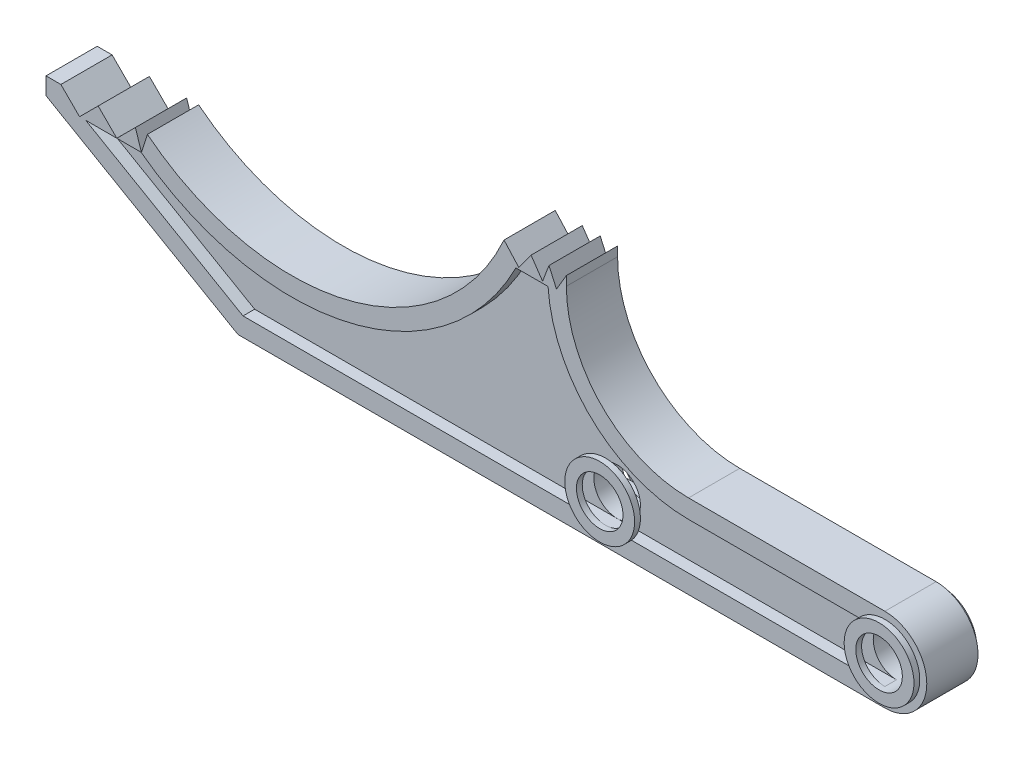
SolidWorks part; units mm, degrees
ref_plane "Front Plane" through (0, 0, 0) normal (0, 0, 1) x (1, 0, 0)
ref_plane "Top Plane" through (0, 0, 0) normal (0, 1, 0) x (1, 0, 0)
ref_plane "Right Plane" through (0, 0, 0) normal (1, 0, 0) x (0, 0, -1)
sketch "Sketch1" plane through (0, 0, 0) normal (0, 0, 1) x (1, 0, 0)
  line L0 (0, 0) -> (70, 0)
  line L1 (0, 0) -> (-22.0836, 12.75)
  line L2 (-22.0836, 12.75) -> (-22.0836, 17.75)
  line L3 (-22.0836, 17.75) -> (-8.4836, 17.75)
  line L4 (27.7864, 27.12) -> (37.7964, 27.12)
  line L5 (70, 0) -> (70, 13) construction
  line L6 (70, 13) -> (48.9164, 13)
  line L7 (37.7964, 27.12) -> (37.7964, 24.12)
  arc A0 (27.7864, 27.12) -> (-8.4836, 17.75) centre (6.3126, 35.3588) cw
  arc A1 (70, 0) -> (70, 13) centre (70, 6.5) ccw
  arc A3 (37.7964, 24.12) -> (48.9164, 13) centre (48.9164, 24.12) ccw
  point P14 (0, 0)
  point P15 (0, 0)
  point P16 (42.0343, 22.6471)
  point P17 (47.0472, 25.7525)
  dimension "D9" = 23
  dimension "D1" = 70
  dimension "D2" = 210
  dimension "D3" = 25.5
  dimension "D4" = 5
  dimension "D5" = 13.6
  dimension "D6" = 27.12
  dimension "D7" = 10.01
  dimension "D8" = 36.27
  dimension "D10" = 13
  dimension "D11" = 3
extrude "Boss-Extrude1" add sketch "Sketch1" along normal mid plane 8
sketch "Sketch3" plane through (0, 0, -4) normal (0, 0, -1) x (-1, 0, 0)
  line L0 (-70, 6.5) -> (-40, 6.5) construction
  circle A2 centre (-70, 6.5) radius 2.5
  circle A3 centre (-40, 6.5) radius 2.5
  dimension "D1" = 5
  dimension "D2" = 5
  dimension "D3" = 30
extrude "Cut-Extrude1" cut sketch "Sketch3" against normal through all
sketch "Sketch4" plane through (0, 0, 4) normal (0, 0, 1) x (1, 0, 0)
  line L14 (-20.0836, 13.9047) -> (0.5359, 2)
  line L15 (0.5359, 2) -> (70, 2)
  line L16 (70, 11) -> (48.9164, 11)
  line L17 (35.7964, 24.12) -> (35.7964, 25.12)
  line L18 (35.7964, 25.12) -> (29.1198, 25.12)
  line L19 (-9.1953, 15.75) -> (-20.0836, 15.75)
  line L20 (-20.0836, 15.75) -> (-20.0836, 13.9047)
  line L21 (-20.0836, 13.9047) -> (0.5359, 2)
  line L22 (0.5359, 2) -> (70, 2)
  line L23 (70, 11) -> (48.9164, 11)
  line L24 (35.7964, 24.12) -> (35.7964, 25.12)
  line L25 (35.7964, 25.12) -> (29.1198, 25.12)
  line L26 (-9.1953, 15.75) -> (-20.0836, 15.75)
  line L27 (-20.0836, 15.75) -> (-20.0836, 13.9047)
  arc A6 (70, 2) -> (70, 11) centre (70, 6.5) ccw
  arc A7 (35.7964, 24.12) -> (48.9164, 11) centre (48.9164, 24.12) ccw
  arc A8 (-9.1953, 15.75) -> (29.1198, 25.12) centre (6.3126, 35.3588) ccw
  arc A9 (70, 2) -> (70, 11) centre (70, 6.5) ccw
  arc A10 (35.7964, 24.12) -> (48.9164, 11) centre (48.9164, 24.12) ccw
  arc A11 (-9.1953, 15.75) -> (29.1198, 25.12) centre (6.3126, 35.3588) ccw
  dimension "D1" = 2
extrude "Cut-Extrude2" cut sketch "Sketch4" against normal blind 1.25
sketch "Sketch5" plane through (0, 0, 2.75) normal (0, 0, 1) x (1, 0, 0)
  circle A0 centre (70, 6.5) radius 2.5 construction
  circle A1 centre (70, 6.5) radius 2.5
  circle A2 centre (40, 6.5) radius 2.5 construction
  circle A3 centre (40, 6.5) radius 2.5
  circle A4 centre (40, 6.5) radius 3.75
  circle A5 centre (70, 6.5) radius 3.75
  dimension "D1" = 1.25
extrude "Boss-Extrude2" add sketch "Sketch5" along normal mid plane 1.25
mirror "Mirror1" about plane through (0, 0, 0) normal (0, 0, 1) of "Cut-Extrude2", "Boss-Extrude2"
sketch "Sketch7" plane through (0, 0, 4) normal (0, 0, 1) x (1, 0, 0)
  line L0 (-22.0836, 17.75) -> (-20.4836, 17.75) construction
  line L1 (-8.4836, 17.75) -> (-22.0836, 17.75) construction
  line L2 (-20.4836, 17.75) -> (-18.4836, 15.75) construction
  line L3 (-9.1953, 15.75) -> (-20.0836, 15.75) construction
  line L4 (-18.4836, 15.75) -> (-16.4836, 17.75) construction
  line L5 (-16.4836, 17.75) -> (-16.4836, 12.6303) construction
  line L6 (-14.4836, 15.75) -> (-16.4836, 17.75) construction
  line L7 (-12.4836, 17.75) -> (-14.4836, 15.75) construction
  line L8 (-12.4836, 17.75) -> (-12.4836, 11.9186) construction
  line L9 (-12.4836, 17.75) -> (-10.4836, 15.75) construction
  line L10 (-10.4836, 15.75) -> (-8.4836, 17.75) construction
  line M5 (0.5359, 2) -> (-20.0836, 13.9047)
  line M6 (-20.0836, 13.9047) -> (-20.0836, 15.75)
  line M7 (-20.0836, 15.75) -> (-9.1953, 15.75)
  arc M8 (-9.1953, 15.75) -> (29.1198, 25.12) centre (6.3126, 35.3588) ccw
  line M9 (29.1198, 25.12) -> (35.7964, 25.12)
  line M10 (35.7964, 25.12) -> (35.7964, 24.12)
  arc M11 (35.7964, 24.12) -> (48.9164, 11) centre (48.9164, 24.12) ccw
  line M12 (48.9164, 11) -> (70, 11)
  arc M13 (70, 11) -> (70, 2) centre (70, 6.5) cw
  line M14 (70, 2) -> (0.5359, 2)
  line M15 (-22.0836, 12.75) -> (0, 0)
  line M16 (0, 0) -> (70, 0)
  arc M17 (70, 0) -> (70, 13) centre (70, 6.5) ccw
  line M18 (70, 13) -> (48.9164, 13)
  arc M19 (48.9164, 13) -> (37.7964, 24.12) centre (48.9164, 24.12) cw
  line M20 (37.7964, 24.12) -> (37.7964, 27.12)
  line M21 (37.7964, 27.12) -> (27.7864, 27.12)
  arc M22 (27.7864, 27.12) -> (-8.4836, 17.75) centre (6.3126, 35.3588) cw
  line M23 (-8.4836, 17.75) -> (-22.0836, 17.75)
  line M24 (-22.0836, 17.75) -> (-22.0836, 12.75)
  dimension "D1" = 1.6
  dimension "D2" = 90
  dimension "D3" = 135
  dimension "D4" = 2.8284
extrude "Cut-Extrude3" cut sketch "Sketch7" against normal through all contours M24 M15 M16 M17 M18 M19 M20 M21 M22 M23 M14 M5 M6 M7 M8 M9 M10 M11 M12 M13 region at (-21.0612, 15.25, 4)
sketch "Sketch8" plane through (0, 0, 2.75) normal (0, 0, 1) x (1, 0, 0)
  line L14 (-15.8157, 13.75) -> (1.0718, 4)
  line L15 (1.0718, 4) -> (70, 4)
  line L16 (70, 9) -> (48.9164, 9)
  line L17 (33.8295, 23.12) -> (30.3794, 23.12)
  line L18 (-9.8756, 13.75) -> (-15.8157, 13.75)
  line L19 (-15.8157, 13.75) -> (1.0718, 4)
  line L20 (1.0718, 4) -> (70, 4)
  line L21 (70, 9) -> (48.9164, 9)
  line L22 (33.8295, 23.12) -> (30.3794, 23.12)
  line L23 (-9.8756, 13.75) -> (-15.8157, 13.75)
  arc A6 (70, 4) -> (70, 9) centre (70, 6.5) ccw
  arc A7 (33.8295, 23.12) -> (48.9164, 9) centre (48.9164, 24.12) ccw
  arc A8 (-9.8756, 13.75) -> (30.3794, 23.12) centre (6.3126, 35.3588) ccw
  arc A9 (70, 4) -> (70, 9) centre (70, 6.5) ccw
  arc A10 (33.8295, 23.12) -> (48.9164, 9) centre (48.9164, 24.12) ccw
  arc A11 (-9.8756, 13.75) -> (30.3794, 23.12) centre (6.3126, 35.3588) ccw
  dimension "D1" = 2
extrude "Cut-Extrude4" cut sketch "Sketch8" against normal blind 1.25
mirror "Mirror2" about plane through (0, 0, 0) normal (0, 0, 1) of "Cut-Extrude4", "Cut-Extrude3"
sketch "Sketch9" plane through (0, 0, 2.75) normal (0, 0, 1) x (1, 0, 0)
  line L0 (-20.0836, 15.75) -> (-18.4836, 15.75) construction
  line L1 (-9.1953, 15.75) -> (-20.0836, 15.75) construction
  line L2 (-18.4836, 15.75) -> (-16.4825, 13.7489)
  line L3 (-16.4825, 13.7489) -> (-14.4814, 15.75)
  line L4 (-16.4825, 13.7489) -> (-9.8392, 13.7489) construction
  line L5 (-14.4814, 15.75) -> (-14.4814, 11.8563) construction
  line L6 (-12.4803, 13.7489) -> (-14.4814, 15.75)
  line L7 (-10.4792, 15.75) -> (-12.4803, 13.7489)
  line L8 (-10.4792, 15.75) -> (-10.4792, 12.8695) construction
  line L9 (-10.4792, 15.75) -> (-9.8392, 13.7489)
  line L10 (-9.8392, 13.7489) -> (-9.1953, 15.75)
  dimension "D1" = 1.6
  dimension "D2" = 135
  dimension "D3" = 2.83
  dimension "D4" = 90
extrude "Cut-Extrude5" cut sketch "Sketch9" against normal through all and the other way through all
sketch "Sketch11" plane through (0, 0, 2.75) normal (0, 0, 1) x (1, 0, 0)
  line L0 (27.8108, 23.32) -> (36.1946, 23.32) construction
  line L1 (33.8295, 23.12) -> (30.3794, 23.12) construction
  line L2 (29.0999, 25.0758) -> (30.6881, 23.32)
  line L3 (30.6881, 23.32) -> (32.0027, 25.12)
  line L4 (35.7964, 25.12) -> (29.1198, 25.12) construction
  line L5 (32.0027, 25.12) -> (33.243, 23.32)
  line L6 (33.243, 23.32) -> (33.9291, 25.12)
  line L7 (33.9291, 25.12) -> (34.7355, 23.32)
  line L8 (34.7355, 23.32) -> (35.7964, 25.12)
  arc A0 (-9.1953, 15.75) -> (29.1198, 25.12) centre (6.3126, 35.3588) ccw construction
  dimension "D1" = 0.2
  dimension "D2" = 78.274
extrude "Cut-Extrude6" cut sketch "Sketch11" against normal through all both and the other way through all
